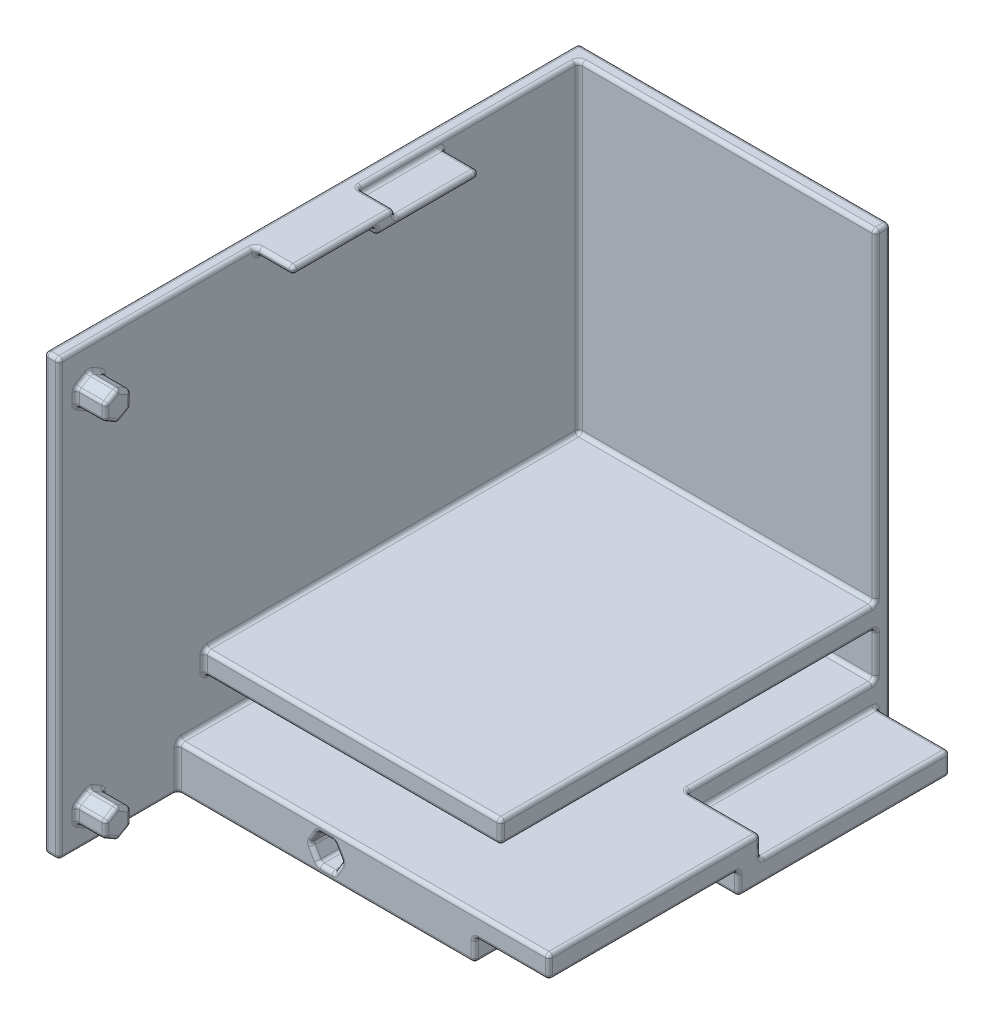
SolidWorks part; units mm, degrees
ref_plane "Front Plane" through (0, 0, 0) normal (0, 0, 1) x (1, 0, 0)
ref_plane "Top Plane" through (0, 0, 0) normal (0, 1, 0) x (1, 0, 0)
ref_plane "Right Plane" through (0, 0, 0) normal (1, 0, 0) x (0, 0, -1)
sketch "Sketch3" plane through (0, 0, 0) normal (1, 0, 0) x (0, 0, -1)
  line L1 (-72, 58.5) -> (72, 58.5)
  line L2 (-72, 58.5) -> (-72, -58.5)
  line L3 (-72, -58.5) -> (72, -58.5)
  line L4 (72, 58.5) -> (72, -58.5)
  line L5 (-72, 58.5) -> (72, -58.5) construction
  line L6 (-72, -58.5) -> (72, 58.5) construction
  point P0 (0, 0)
  dimension "D1" = 117
  dimension "D2" = 144
extrude "Boss-Extrude2" add sketch "Sketch3" along normal blind 4
sketch "Sketch5" plane through (0, 0, 0) normal (-1, 0, 0) x (0, 0, 1)
  line L6 (-72, 56.5) -> (64, 56.5) construction
  line L7 (-72, -58.5) -> (-72, 58.5) construction
  line L23 (-72, 58.5) -> (72, 58.5) construction
  line L25 (64, 56.5) -> (56, 56.5)
  line L29 (64, -53.6739) -> (64, -45.6739) construction
  line L31 (60.5359, -47.6739) -> (64, -45.6739)
  line L32 (64, 43.6739) -> (67.4641, 45.6739)
  line L33 (67.4641, 45.6739) -> (67.4641, 49.6739)
  line L34 (67.4641, 49.6739) -> (64, 51.6739)
  line L35 (64, 51.6739) -> (60.5359, 49.6739)
  line L36 (60.5359, 49.6739) -> (60.5359, 45.6739)
  line L37 (60.5359, 45.6739) -> (64, 43.6739)
  line L38 (60.5359, -51.6739) -> (60.5359, -47.6739)
  line L39 (64, -53.6739) -> (60.5359, -51.6739)
  line L40 (67.4641, -51.6739) -> (64, -53.6739)
  line L41 (67.4641, -47.6739) -> (67.4641, -51.6739)
  line L42 (64, -45.6739) -> (67.4641, -47.6739)
  line L43 (64, 43.6739) -> (64, 44.2098) construction
  line L44 (64, 51.138) -> (64, 51.6739) construction
  circle A0 centre (64, 47.6739) radius 3.4641 construction
  circle A1 centre (64, -49.6739) radius 3.4641 construction
  dimension "D1" = 2
  dimension "D3" = 4
extrude "Boss-Extrude3" add sketch "Sketch5" against normal blind 12 contours L42 L31 L38 L39 L40 L41 | L36 L37 L32 L33 L34 L35
sketch "Sketch6" plane through (4, 0, 0) normal (1, 0, 0) x (0, 0, -1)
  line L6 (-19, 58.5) -> (-19, 56.5)
  line L7 (3.5, 54.5) -> (31, 54.5) construction
  line L9 (-19, 58.5) -> (8.5, 58.5)
  line L11 (3.5, 54.5) -> (31, 54.5)
  line L12 (31, 56.5) -> (31, 54.5)
  line L15 (3.5, 56.5) -> (3.5, 54.5)
  line L16 (8.5, 58.5) -> (8.5, 56.5)
  line L17 (-19, 56.5) -> (3.5, 56.5)
  line L19 (8.5, 56.5) -> (31, 56.5)
  point P16 (6, 56.5)
  dimension "D7" = 22.5
extrude "Boss-Extrude4" add sketch "Sketch6" along normal blind 10
sketch "Sketch7" plane through (4, 0, 0) normal (1, 0, 0) x (0, 0, -1)
  line L0 (-72, -58.5) -> (72, -58.5) construction
  line L1 (72, 58.5) -> (68, 58.5)
  line L2 (72, 58.5) -> (72, -58.5)
  line L3 (72, -58.5) -> (68, -58.5)
  line L4 (68, 58.5) -> (68, -58.5)
  dimension "D1" = 4
extrude "Boss-Extrude5" add sketch "Sketch7" along normal blind 80
sketch "Sketch8" plane through (4, 0, 0) normal (1, 0, 0) x (0, 0, -1)
  line L14 (68, -58.5) -> (-40, -58.5)
  line L15 (68, -58.5) -> (68, -46.5)
  line L20 (68, -46.5) -> (-40, -46.5)
  line L21 (-40, -58.5) -> (-40, -46.5)
  dimension "D1" = 12
  dimension "D2" = 108
sketch "Sketch9" plane through (84, 0, 0) normal (1, 0, 0) x (0, 0, -1)
  line L9 (-40, -46.5) -> (17, -46.5)
  line L13 (-40, -52.5) -> (-40, -46.5)
  line L14 (68, -52.5) -> (68, -58.5)
  line L15 (68, -58.5) -> (72, -58.5) construction
  line L16 (68, -58.5) -> (11, -58.5)
  line L17 (11, -58.5) -> (11, -52.5)
  line L18 (11, -52.5) -> (-40, -52.5)
  line L19 (68, -52.5) -> (17, -52.5)
  line L20 (17, -52.5) -> (17, -46.5)
  dimension "D2" = 57
  dimension "D3" = 57
extrude "Boss-Extrude8" add sketch "Sketch9" along normal blind 20
extrude "Boss-Extrude9" add sketch "Sketch8" along normal blind 80
sketch "Sketch10" plane through (0, 0, 40) normal (0, 0, 1) x (1, 0, 0)
  line L0 (4, -52.5) -> (44, -52.5)
  line L1 (4, -46.5) -> (4, -58.5) construction
  line L2 (44, -52.5) -> (44, -58.5)
  line L3 (84, -58.5) -> (4, -58.5) construction
  line L5 (48.2, -52.5) -> (46.1, -48.8627)
  line L6 (46.1, -48.8627) -> (41.9, -48.8627)
  line L7 (41.9, -48.8627) -> (39.8, -52.5)
  line L8 (39.8, -52.5) -> (41.9, -56.1373)
  line L9 (41.9, -56.1373) -> (46.1, -56.1373)
  line L10 (46.1, -56.1373) -> (48.2, -52.5)
  circle A0 centre (44, -52.5) radius 3.6373 construction
  dimension "D1" = 40
  dimension "D2" = 6
  dimension "D3" = 4.2
extrude "Cut-Extrude1" cut sketch "Sketch10" against normal blind 10 contours L9 L10 L5 L6 L7 L0 L2 | L8 L9 L2 L0
sketch "Sketch12" plane through (0, 0, -72) normal (0, 0, -1) x (-1, 0, 0)
  line L0 (0, -58.5) -> (0, 58.5) construction
  line L2 (-84, -34.5) -> (-84, -28.5)
  line L3 (-84, -28.5) -> (0, -28.5)
  line L4 (0, -34.5) -> (0, -28.5)
  line L5 (-84, -34.5) -> (0, -34.5)
  dimension "D2" = 6
extrude "Boss-Extrude10" add sketch "Sketch12" against normal blind 105
fillet "Fillet2" radius 1 127 edges at (42, 58.5, -72) (2, 58.5, 72) (2, -58.5, 72) (42, -58.5, -72) (4, -58.5, 56) (4, 0, 72) (4, 58.5, -38.25) (4, 58.5, 45.5) (0, -58.5, 0) (0, 0, 72) (0, 58.5, 0) (0, 0, -72) (4, -46.6739, 65.7321) (4, -49.6739, 67.4641) (4, -52.6739, 65.7321) (4, -52.6739, 62.2679) (4, -49.6739, 60.5359) (4, -46.6739, 62.2679) (8, -47.6739, 67.4641) (8, -51.6739, 67.4641) (8, -53.6739, 64) (8, -51.6739, 60.5359) (8, -47.6739, 60.5359) (8, -45.6739, 64) (12, -49.6739, 67.4641) (12, -52.6739, 65.7321) (12, -52.6739, 62.2679) (12, -49.6739, 60.5359) (12, -46.6739, 62.2679) (12, -46.6739, 65.7321) (4, 47.6739, 60.5359) (4, 50.6739, 62.2679) (4, 50.6739, 65.7321) (4, 47.6739, 67.4641) (4, 44.6739, 65.7321) (4, 44.6739, 62.2679) (8, 49.6739, 60.5359) (8, 51.6739, 64) (8, 49.6739, 67.4641) (8, 45.6739, 67.4641) (8, 43.6739, 64) (8, 45.6739, 60.5359) (12, 50.6739, 62.2679) (12, 50.6739, 65.7321) (12, 47.6739, 67.4641) (12, 44.6739, 65.7321) (12, 44.6739, 62.2679) (12, 47.6739, 60.5359) (9, 56.5, -3.5) (9, 54.5, -3.5) (9, 54.5, -31) (9, 56.5, -31) (9, 56.5, -8.5) (9, 58.5, -8.5) (9, 58.5, 19) (9, 56.5, 19) (14, 58.5, 5.25) (14, 56.5, -19.75) (14, 54.5, -17.25) (14, 56.5, 7.75) (4, 56.5, -19.75) (4, 54.5, -17.25) (4, 56.5, 7.75) (44, 58.5, -68) (84, -58.5, 14.5) (84, -58.5, -70) (84, 15, -68) (84, -40.5, -68) (84, 58.5, -70) (84, 0, -72) (4, 15, -68) (4, -40.5, -68) (44, -46.5, -68) (54, -46.5, 40) (44, -58.5, 40) (84, -55.5, 40) (84, -46.5, -42.5) (4, -52.5, 40) (4, -46.5, -14) (94, -52.5, -17) (94, -46.5, -17) (94, -52.5, 40) (94, -52.5, -11) (94, -58.5, -11) (94, -58.5, -68) (94, -52.5, -68) (104, -55.5, -68) (104, -58.5, -39.5) (104, -55.5, -11) (104, -52.5, 14.5) (104, -49.5, 40) (104, -46.5, 11.5) (104, -49.5, -17) (104, -52.5, -42.5) (84, -55.5, -68) (84, -55.5, -11) (84, -52.5, 14.5) (84, -49.5, -17) (84, -52.5, -42.5) (41.9, -56.1373, 35) (39.8, -52.5, 35) (41.9, -48.8627, 35) (46.1, -48.8627, 35) (48.2, -52.5, 35) (46.1, -56.1373, 35) (40.85, -54.3187, 30) (40.85, -50.6813, 30) (44, -48.8627, 30) (47.15, -50.6813, 30) (47.15, -54.3187, 30) (44, -56.1373, 30) (40.85, -54.3187, 40) (40.85, -50.6813, 40) (44, -48.8627, 40) (47.15, -50.6813, 40) (47.15, -54.3187, 40) (44, -56.1373, 40) (4, -34.5, -17.5) (44, -34.5, -68) (4, -28.5, -17.5) (44, -28.5, -68) (4, -31.5, 33) (84, -34.5, -17.5) (84, -28.5, -17.5) (44, -34.5, 33) (84, -31.5, 33) (44, -28.5, 33)
